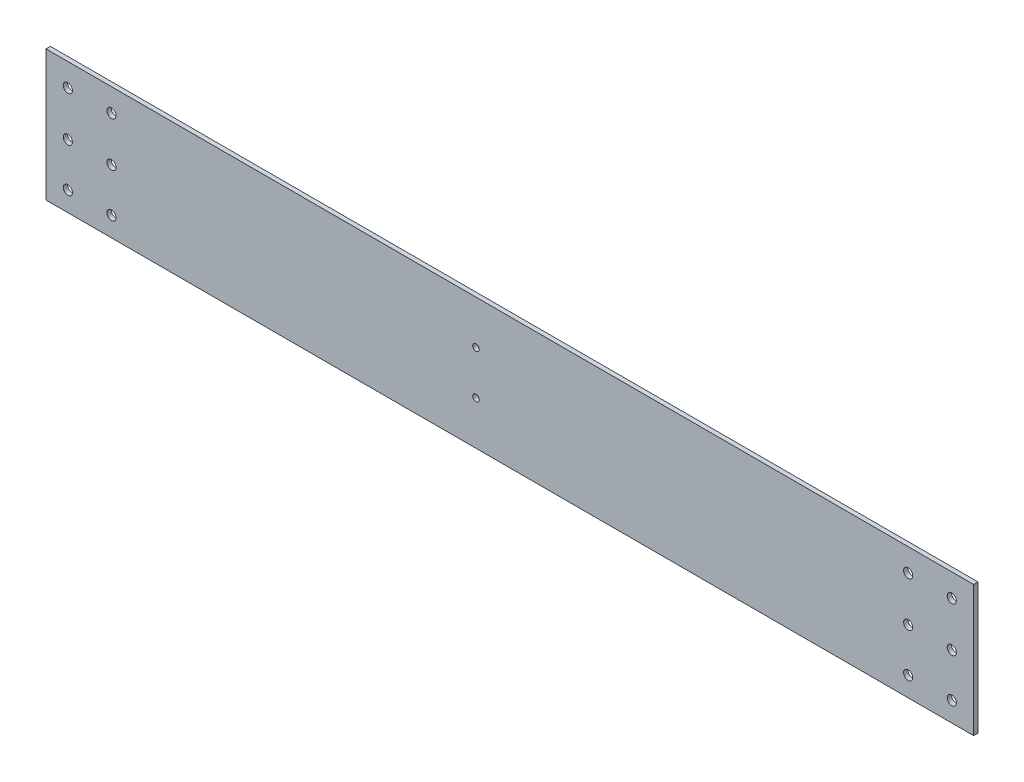
SolidWorks part; units mm, degrees
material "Thornel Mat VMA"
ref_plane "前视基准面" through (0, 0, 0) normal (0, 0, 1) x (1, 0, 0)
ref_plane "上视基准面" through (0, 0, 0) normal (0, 1, 0) x (1, 0, 0)
ref_plane "右视基准面" through (0, 0, 0) normal (1, 0, 0) x (0, 0, -1)
other "Configuration Table"
sketch "草图1" plane through (0, 0, 0) normal (0, 0, 1) x (1, 0, 0)
  line L1 (-212.5, 30) -> (212.5, 30)
  line L2 (-212.5, 30) -> (-212.5, -30)
  line L3 (-212.5, -30) -> (212.5, -30)
  line L4 (212.5, 30) -> (212.5, -30)
  line L5 (0, -30) -> (0, 30) construction
  line L6 (-212.5, 0) -> (212.5, 0) construction
  point P0 (0, 0)
  dimension "D1" = 425
  dimension "D2" = 60
extrude "凸台-拉伸1" add sketch "草图1" along normal blind 2
sketch "草图2" plane through (0, 0, 0) normal (0, 0, -1) x (-1, 0, 0)
  circle A0 centre (202.5, -21) radius 2.1 construction
  circle A1 centre (182.5, -21) radius 2.1 construction
  circle A2 centre (202.5, 19.5) radius 2.1 construction
  circle A3 centre (202.5, -1) radius 2.1 construction
  circle A4 centre (182.5, -1) radius 2.1 construction
  circle A5 centre (182.5, 19.5) radius 2.1 construction
  circle A6 centre (202.5, -21) radius 2.1
  circle A7 centre (182.5, -21) radius 2.1
  circle A8 centre (202.5, 19.5) radius 2.1
  circle A9 centre (202.5, -1) radius 2.1
  circle A10 centre (182.5, -1) radius 2.1
  circle A11 centre (182.5, 19.5) radius 2.1
  circle A12 centre (-182.5, -21) radius 2.1 construction
  circle A13 centre (-202.5, -21) radius 2.1 construction
  circle A14 centre (-182.5, -1) radius 2.1 construction
  circle A15 centre (-202.5, -1) radius 2.1 construction
  circle A16 centre (-202.5, 19.5) radius 2.1 construction
  circle A17 centre (-182.5, 19.5) radius 2.1 construction
  circle A18 centre (15.5, -10) radius 1.5 construction
  circle A19 centre (15.5, 10) radius 1.5 construction
  circle A20 centre (-182.5, -21) radius 2.1
  circle A21 centre (-202.5, -21) radius 2.1
  circle A22 centre (-182.5, -1) radius 2.1
  circle A23 centre (-202.5, -1) radius 2.1
  circle A24 centre (-202.5, 19.5) radius 2.1
  circle A25 centre (-182.5, 19.5) radius 2.1
  circle A26 centre (15.5, -10) radius 1.5
  circle A27 centre (15.5, 10) radius 1.5
extrude "切除-拉伸1" cut sketch "草图2" against normal through all
